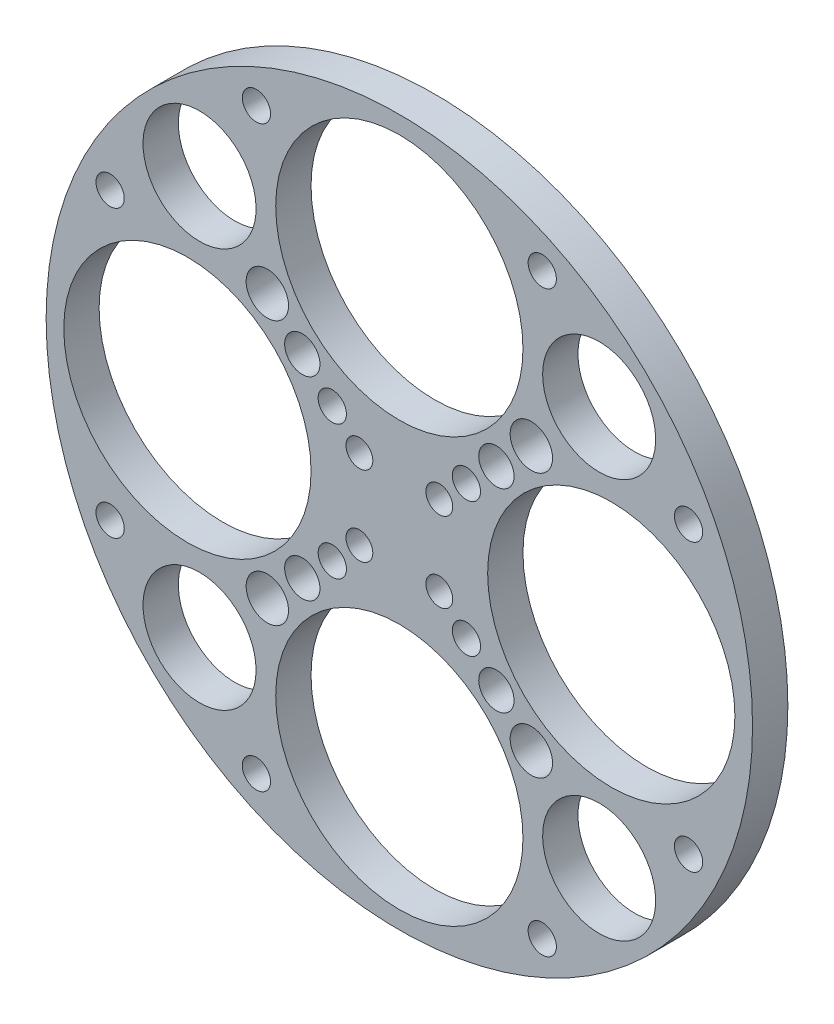
SolidWorks part; units mm, degrees
material "Acrylic (Medium-high impact)"
ref_plane "Front Plane" through (0, 0, 0) normal (0, 0, 1) x (1, 0, 0)
ref_plane "Top Plane" through (0, 0, 0) normal (0, 1, 0) x (1, 0, 0)
ref_plane "Right Plane" through (0, 0, 0) normal (1, 0, 0) x (0, 0, -1)
sketch "Sketch1" plane through (0, 0, 0) normal (0, 0, 1) x (1, 0, 0)
  circle A0 centre (0, 0) radius 50
  dimension "D1" = 100
extrude "Boss-Extrude1" add sketch "Sketch1" along normal blind 5
sketch "Sketch2" plane through (0, 0, 0) normal (0, 0, -1) x (-1, 0, 0)
  line L0 (0, 0) -> (0, 50) construction
  line L1 (-5.6569, 5.6569) -> (0, 0) construction
  circle A0 centre (-5.6569, 5.6569) radius 1.9
  circle A1 centre (0, 0) radius 50 construction
  dimension "D1" = 3.8
  dimension "D2" = 8
  dimension "D3" = 45
extrude "Cut-Extrude1" cut sketch "Sketch2" against normal through all
pattern_circular "CirPattern1" count 4 over 360 about axis through (0, 0, 5) along (0, 0, -1) of "Cut-Extrude1"
sketch "Sketch3" plane through (0, 0, 0) normal (0, 0, -1) x (-1, 0, 0)
  circle A0 centre (0, 30) radius 17.5
  circle A1 centre (-5.6569, 5.6569) radius 4 construction
  dimension "D1" = 8
  dimension "D2" = 35
  dimension "D3" = 30
extrude "Cut-Extrude2" cut sketch "Sketch3" against normal through all
pattern_circular "CirPattern2" count 4 over 360 about axis through (0, 0, 5) along (0, 0, -1) of "Cut-Extrude2"
sketch "Sketch4" plane through (0, 0, 0) normal (0, 0, -1) x (-1, 0, 0)
  line L0 (-30, 0) -> (-30, 30) construction
  line L1 (0, 30) -> (-30, 30) construction
  line L2 (-30, 30) -> (0, 0) construction
  circle A0 centre (-28.2843, 28.2843) radius 8
  circle A1 centre (-18.6863, 18.6863) radius 3
  circle A2 centre (-13.7365, 13.7365) radius 2.5
  circle A3 centre (-9.4939, 9.4939) radius 2
  circle A4 centre (-20.2318, 40.9396) radius 2
  circle A5 centre (0, 30) radius 17.5 construction
  circle A6 centre (-40.9396, 20.2318) radius 2
  dimension "D1" = 16
  dimension "D2" = 40
  dimension "D3" = 6
  dimension "D5" = 5
  dimension "D6" = 7
  dimension "D7" = 4
  dimension "D8" = 6
  dimension "D9" = 4
  dimension "D10" = 23
  dimension "D11" = 15
  dimension "D12" = 4
  dimension "D13" = 15
  dimension "D14" = 23
  dimension "D4" = 16
extrude "Cut-Extrude3" cut sketch "Sketch4" against normal through all
pattern_circular "CirPattern3" count 4 over 360 about axis through (0, 0, 5) along (0, 0, -1) of "Cut-Extrude3"
